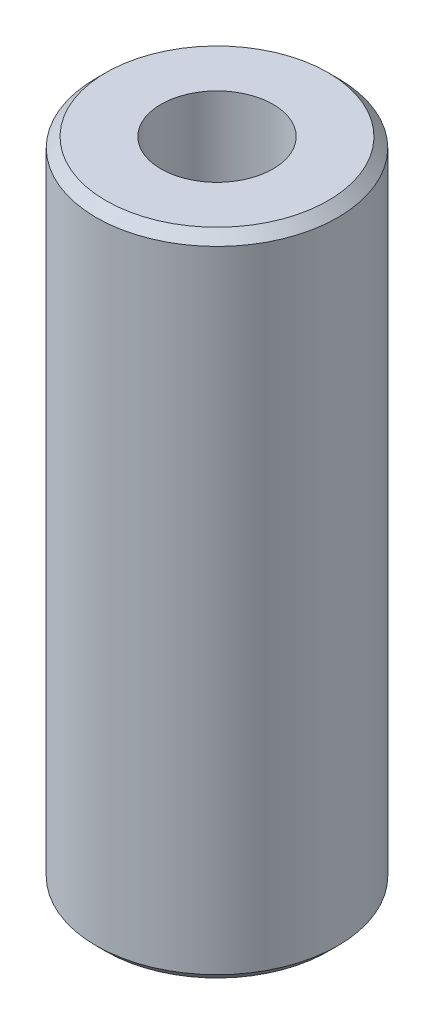
SolidWorks part; units mm, degrees
ref_plane "Front Plane" through (0, 0, 0) normal (0, 0, 1) x (1, 0, 0)
ref_plane "Top Plane" through (0, 0, 0) normal (0, 1, 0) x (1, 0, 0)
ref_plane "Right Plane" through (0, 0, 0) normal (1, 0, 0) x (0, 0, -1)
sketch "Sketch1" plane through (0, 0, 0) normal (0, 1, 0) x (1, 0, 0)
  circle A0 centre (0, 0) radius 57.5
  dimension "SHAFT_OD" = 115
extrude "Boss-Extrude1" add sketch "Sketch1" along normal blind 309.5848
sketch "Sketch2" plane through (0, 0, 0) normal (0, 1, 0) x (1, 0, 0)
  circle A0 centre (0, 0) radius 26.685
  dimension "BORE_D" = 53.37
extrude "Cut-Extrude1" cut sketch "Sketch2" along normal through all
chamfer "Chamfer1" distance 4.6386 angle 45 2 edges at (0, 309.5848, 57.5) (0, 0, 57.5)
